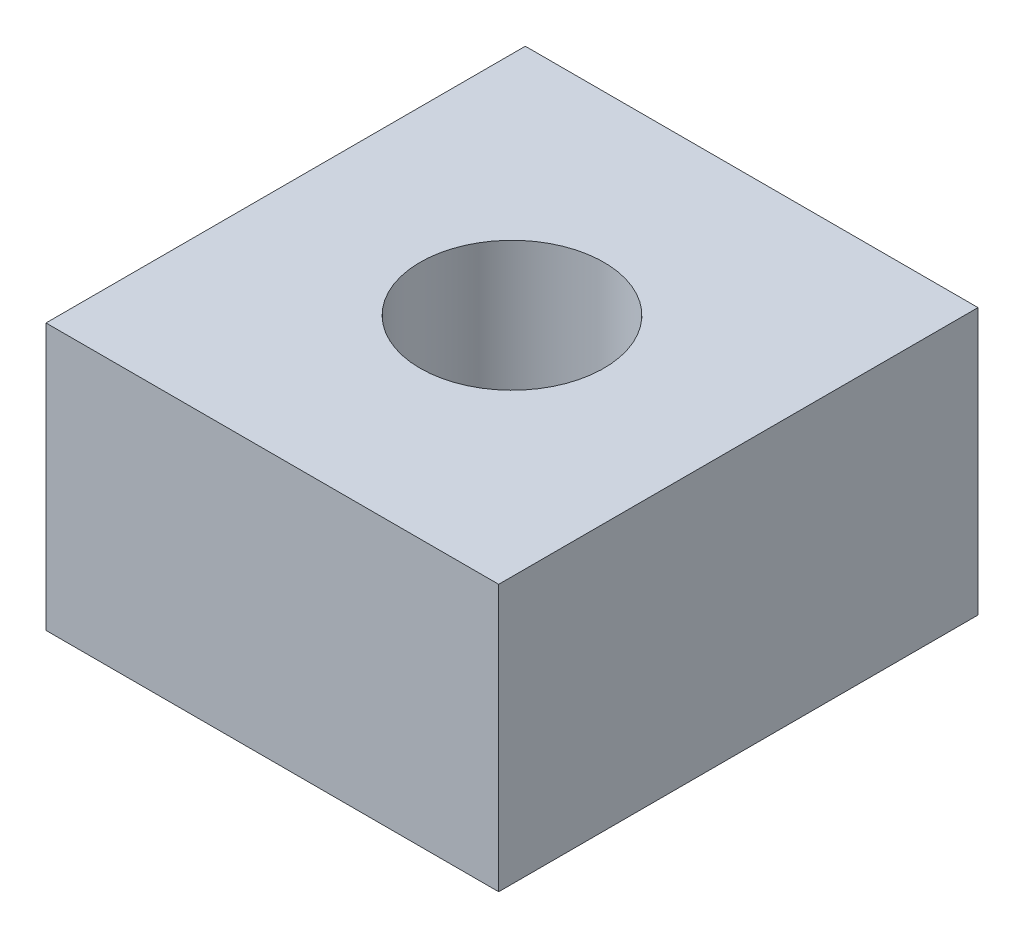
SolidWorks part; units mm, degrees
ref_plane "Front Plane" through (0, 0, 0) normal (0, 0, 1) x (1, 0, 0)
ref_plane "Top Plane" through (0, 0, 0) normal (0, 1, 0) x (1, 0, 0)
ref_plane "Right Plane" through (0, 0, 0) normal (1, 0, 0) x (0, 0, -1)
sketch "Sketch1" plane through (0, 0, 0) normal (0, 1, 0) x (1, 0, 0)
  line L1 (0, 0) -> (17, 0)
  line L2 (0, 0) -> (0, 18)
  line L3 (0, 18) -> (17, 18)
  line L4 (17, 0) -> (17, 18)
  dimension "D1" = 18
  dimension "D2" = 17
extrude "Boss-Extrude1" add sketch "Sketch1" along normal blind 10
sketch "Sketch2" plane through (0, 10, 0) normal (0, 1, 0) x (1, 0, 0)
  line L0 (0, 18) -> (17, 0) construction
  circle A0 centre (8.5, 9) radius 3.45
  point P6 (8.5, 9)
  dimension "D1" = 6.9
extrude "Cut-Extrude1" cut sketch "Sketch2" against normal blind 10
